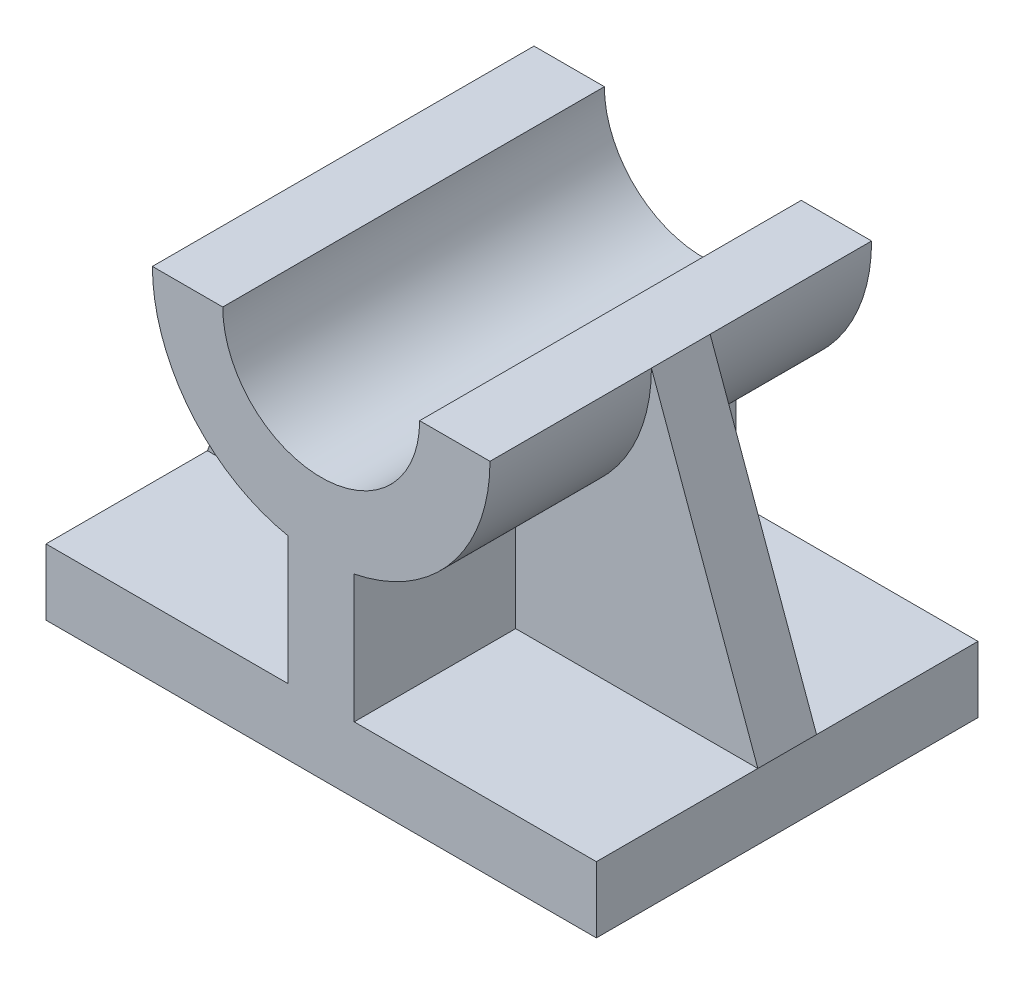
SolidWorks part; units mm, degrees
ref_plane "Front Plane" through (0, 0, 0) normal (0, 0, 1) x (1, 0, 0)
ref_plane "Top Plane" through (0, 0, 0) normal (0, 1, 0) x (1, 0, 0)
ref_plane "Right Plane" through (0, 0, 0) normal (1, 0, 0) x (0, 0, -1)
sketch "Sketch1" plane through (0, 0, 0) normal (0, 0, 1) x (1, 0, 0)
  line L0 (-37.5, 0) -> (37.5, 0)
  line L1 (37.5, 0) -> (37.5, 9)
  line L2 (37.5, 9) -> (4.5, 9)
  line L6 (-4.5, 9) -> (-37.5, 9)
  line L7 (-37.5, 9) -> (-37.5, 0)
  line L8 (0, 0) -> (0, 65.5262) construction
  line L10 (-23, 49) -> (-13.4155, 49)
  line L11 (-4.5, 9) -> (-4.5, 26.4445)
  line L12 (4.5, 9) -> (4.5, 26.4445)
  line L13 (13.4155, 49) -> (23, 49)
  line L14 (23, 49) -> (37.5, 9)
  line L15 (-23, 49) -> (-37.5, 9)
  arc A0 (-4.5, 26.4445) -> (-23, 49) centre (0, 49) cw
  arc A1 (4.5, 26.4445) -> (23, 49) centre (0, 49) ccw
  arc A2 (13.4155, 49) -> (-13.4155, 49) centre (0, 49) cw
  point P4 (0, 0)
  dimension "D1" = 75
  dimension "D2" = 33
  dimension "D3" = 33
  dimension "D4" = 9
  dimension "D5" = 9
  dimension "D7" = 40
extrude "Boss-Extrude1" add sketch "Sketch1" along normal mid plane 52 contours L8 L0 L1 L2 L12 A1 L13 A2 | L0 L8 A2 L10 A0 L11 L6 L7 region at (-36.883, 4.5, 0) region at (0.617, 17.7922, 0)
extrude "Boss-Extrude2" add sketch "Sketch1<3>" along normal mid plane 8 contours A1 L12 L2 L14 | L11 A0 L15 L6 region at (-20.1038, 21.6041, 0) region at (20.1038, 21.6041, 0)
sketch "Sketch1<3>" plane through (0, 0, 0) normal (0, 0, 1) x (1, 0, 0) same geometry as "Sketch1"
